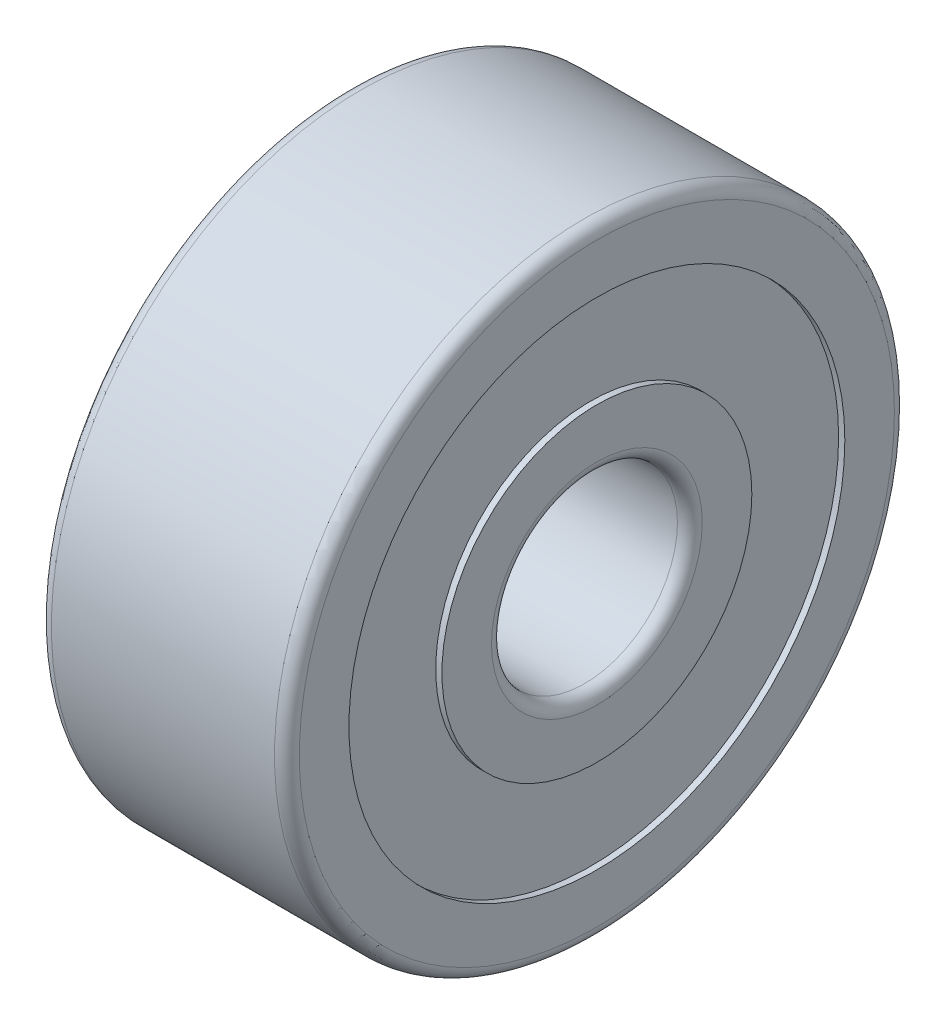
SolidWorks part; units mm, degrees
ref_plane "Front Plane" through (0, 0, 0) normal (0, 0, 1) x (1, 0, 0)
ref_plane "Top Plane" through (0, 0, 0) normal (0, 1, 0) x (1, 0, 0)
ref_plane "Right Plane" through (0, 0, 0) normal (1, 0, 0) x (0, 0, -1)
sketch "Sketch1" plane through (0, 0, 0) normal (1, 0, 0) x (0, 0, -1)
  circle A0 centre (0, 0) radius 5
  circle A1 centre (0, 0) radius 1.5
  dimension "D1" = 10
  dimension "D2" = 3
extrude "Boss-Extrude1" add sketch "Sketch1" along normal blind 2 and the other way blind 2
fillet "Fillet1" radius 0.2 4 edges at (-2, 0, -1.5) (2, 0, -1.5) (-2, 0, -5) (2, 0, -5)
sketch "Sketch2" plane through (2, 0, 0) normal (1, 0, 0) x (0, 0, -1)
  circle A0 centre (0, 0) radius 2.5
  circle A1 centre (0, 0) radius 4
  circle A2 centre (0, 0) radius 5 construction
  circle A3 centre (0, 0) radius 1.5 construction
  dimension "D1" = 1
  dimension "D2" = 1
extrude "Cut-Extrude1" cut sketch "Sketch2" against normal blind 0.1
sketch "Sketch3" plane through (-2, 0, 0) normal (-1, 0, 0) x (0, 0, 1)
  circle A1 centre (0, 0) radius 4
  circle A2 centre (0, 0) radius 4
  circle A3 centre (0, 0) radius 2.5
  circle A4 centre (0, 0) radius 2.5
  dimension "D1" = 0
  dimension "D2" = 0
extrude "Cut-Extrude2" cut sketch "Sketch3" against normal blind 0.1
